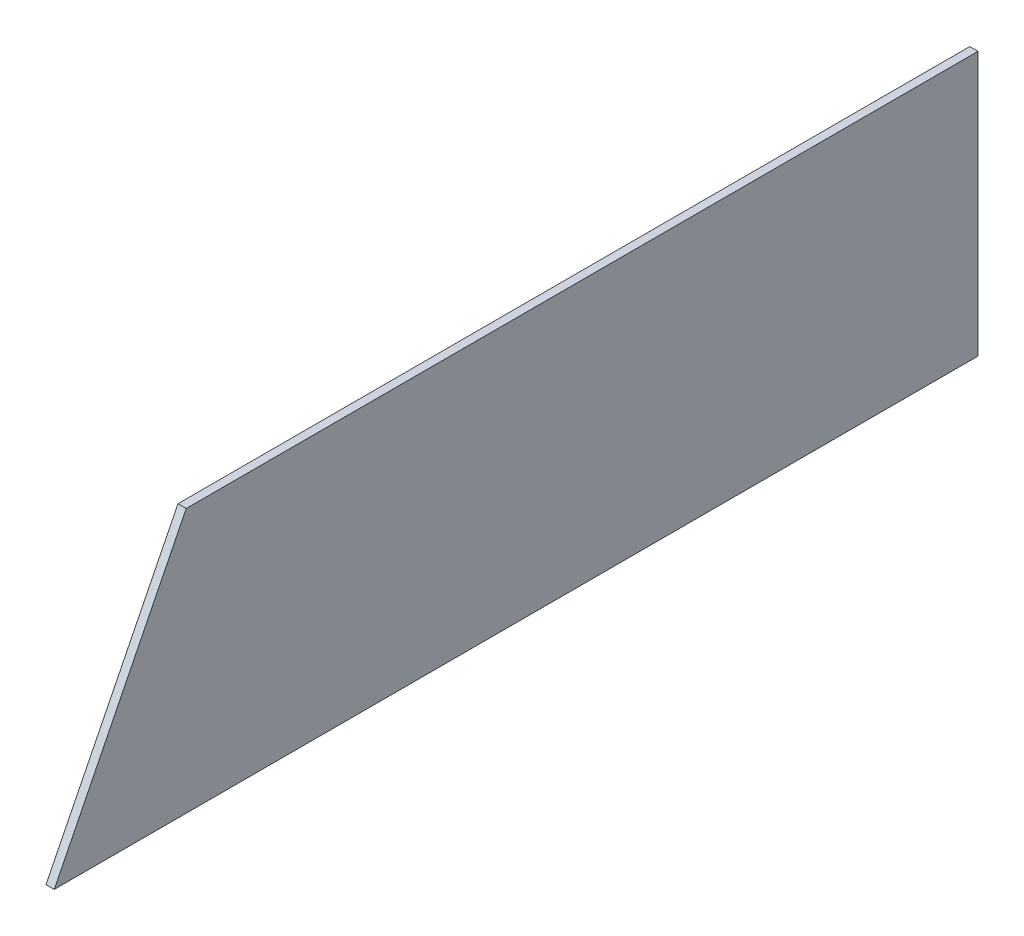
SolidWorks part; units mm, degrees
ref_plane "Front Plane" through (0, 0, 0) normal (0, 0, 1) x (1, 0, 0)
ref_plane "Top Plane" through (0, 0, 0) normal (0, 1, 0) x (1, 0, 0)
ref_plane "Right Plane" through (0, 0, 0) normal (1, 0, 0) x (0, 0, -1)
sketch "Sketch1" plane through (0, 0, 0) normal (1, 0, 0) x (0, 0, -1)
  line L1 (-177.8, -50.8) -> (177.8, -50.8)
  line L2 (-177.8, -50.8) -> (-177.8, 50.8)
  line L3 (-177.8, 50.8) -> (177.8, 50.8)
  line L4 (177.8, -50.8) -> (177.8, 50.8)
  line L5 (-177.8, -50.8) -> (177.8, 50.8) construction
  line L6 (-177.8, 50.8) -> (177.8, -50.8) construction
  point P0 (0, 0)
  dimension "D1" = 355.6
  dimension "D2" = 101.6
extrude "Boss-Extrude1" add sketch "Sketch1" along normal blind 3.175
sketch "Sketch2" plane through (3.175, 0, 0) normal (1, 0, 0) x (0, 0, -1)
  line L0 (-177.8, -50.8) -> (-127, 50.8)
  line L1 (177.8, 50.8) -> (-177.8, 50.8) construction
  dimension "D1" = 50.8
extrude "Cut-Extrude1" cut sketch "Sketch2" against normal blind 3.175 and the other way through all
